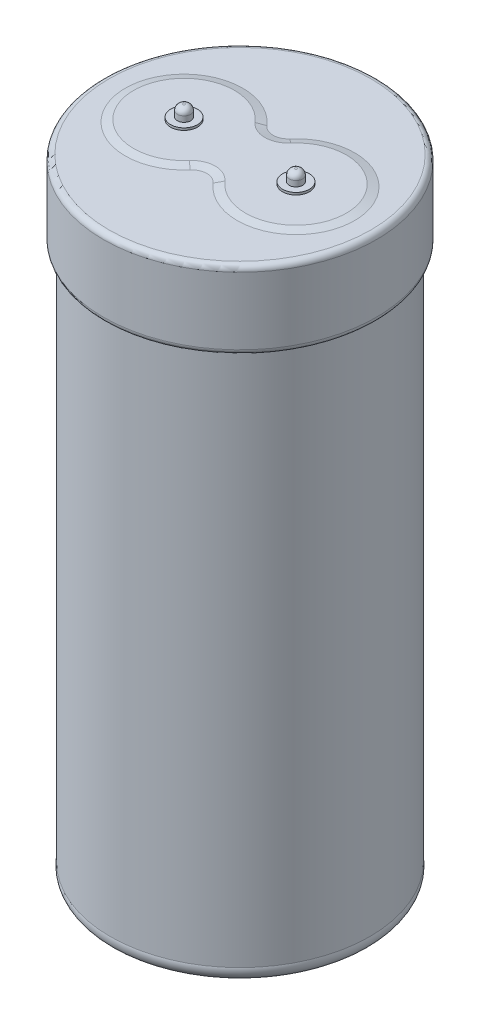
SolidWorks part; units mm, degrees
ref_plane "Front Plane" through (0, 0, 0) normal (0, 0, 1) x (1, 0, 0)
ref_plane "Top Plane" through (0, 0, 0) normal (0, 1, 0) x (1, 0, 0)
ref_plane "Right Plane" through (0, 0, 0) normal (1, 0, 0) x (0, 0, -1)
sketch "Sketch1" plane through (0, 0, 0) normal (0, 0, 1) x (1, 0, 0)
  line L0 (0, 125.4241) -> (0, -154.5759) construction
  line L1 (-1006.3009, 386.8456) -> (941.4092, 386.8456) construction
  line L2 (0, 125.4241) -> (61, 125.4241)
  line L3 (58, 90.4241) -> (58, -148.2441)
  line L4 (53.0864, -154.5759) -> (6, -154.5759)
  line L5 (0, -154.5759) -> (0, 125.4241) construction
  line L6 (6, -154.5759) -> (6, -169.7633)
  line L7 (6, -169.7633) -> (5.1874, -170.5759)
  line L8 (5.1874, -170.5759) -> (0, -170.5759)
  line L9 (0, -170.5759) -> (0, -154.5759) construction
  line L10 (6, -154.5759) -> (0, -154.5759) construction
  line L11 (61, 123.3205) -> (61, 110.2818) construction
  line L12 (0, 125.4241) -> (0, -170.5759)
  line L13 (61, 125.4241) -> (61, 90.4241)
  line L14 (61, 90.4241) -> (58, 90.4241)
  arc A1 (58, -148.2441) -> (53.0864, -154.5759) centre (53.0864, -149.5035) cw
  dimension "D2" = 58
  dimension "D1" = 280
  dimension "D3" = 16
  dimension "D4" = 61
  dimension "D5" = 6
  dimension "D6" = 45
  dimension "D7" = 35
revolve "Revolve1" add sketch "Sketch1" angle 360 about L12
sketch "Sketch2" plane through (0, 125.4241, 0) normal (0, 1, 0) x (1, 0, 0)
  line L0 (-378.6014, 458.2154) -> (210.732, 458.2154) construction
  line L1 (-25, 0) -> (-1.25, 0) construction
  line L2 (0, 45.9854) -> (0, -10.1484) construction
  line L3 (-1.25, 0) -> (0, 0) construction
  line L4 (0, 0) -> (25, 0) construction
  circle A0 centre (25, 0) radius 6
  circle A1 centre (-25, 0) radius 6
  circle A2 centre (25, 0) radius 22.5 construction
  arc A3 (5.1136, 17.1346) -> (-5.1136, 17.1346) centre (0, 21.5407) cw
  arc A4 (5.1136, -17.1346) -> (5.1136, 17.1346) centre (25, 0) ccw
  arc A5 (0, 8.0039) -> (-1.25, 0) centre (25, 0) ccw construction
  arc A6 (-1.25, 0) -> (0, -8.0039) centre (25, 0) ccw construction
  arc A7 (5.1136, 17.1346) -> (0, 8.0039) centre (25, 0) ccw construction
  arc A8 (5.1136, -17.1346) -> (-5.1136, -17.1346) centre (0, -21.5407) ccw
  arc A9 (0, -8.0039) -> (5.1136, -17.1346) centre (25, 0) ccw construction
  arc A10 (-5.1136, -17.1346) -> (-5.1136, 17.1346) centre (-25, 0) cw
  point P6 (0, 0)
  dimension "D1" = 12
  dimension "D2" = 50
  dimension "D3" = 45
  dimension "D4" = 52.5
  dimension "D5" = 6.75
extrude "Boss-Extrude1" add sketch "Sketch2" along normal blind 1
sketch "Sketch3" plane through (0, 125.4241, 0) normal (0, 1, 0) x (1, 0, 0)
  circle A0 centre (-25, 0) radius 6 construction
  circle A1 centre (25, 0) radius 6 construction
  circle A2 centre (-25, 0) radius 6
  circle A3 centre (25, 0) radius 6
extrude "Boss-Extrude2" add sketch "Sketch3" along normal blind 2
sketch "Sketch4" plane through (0, 127.4241, 0) normal (0, 1, 0) x (1, 0, 0)
  line L0 (0, 7.5141) -> (0, -4.8063) construction
  circle A1 centre (25, 0) radius 3
  circle A2 centre (-25, 0) radius 3
  circle A3 centre (-25, 0) radius 3
  dimension "D1" = 3
extrude "Boss-Extrude3" add sketch "Sketch4" along normal blind 5
fillet "Fillet1" radius 2.5 2 edges at (28, 132.4241, 0) (-28, 132.4241, 0)
fillet "Fillet2" radius 2.5 2 edges at (0, 90.4241, 61) (0, 125.4241, 61)
chamfer "Chamfer1" distance 1 angle 75 4 edges at (51.25, 126.4241, 0) (0, 126.4241, -14.7907) (0, 126.4241, 14.7907) (-51.25, 126.4241, 0) first distance on face at (28.1818, 125.9241, 0) first distance on face at (0, 125.9241, -15.9626) first distance on face at (0, 125.9241, 15.9626) first distance on face at (-28.1818, 125.9241, 0)
